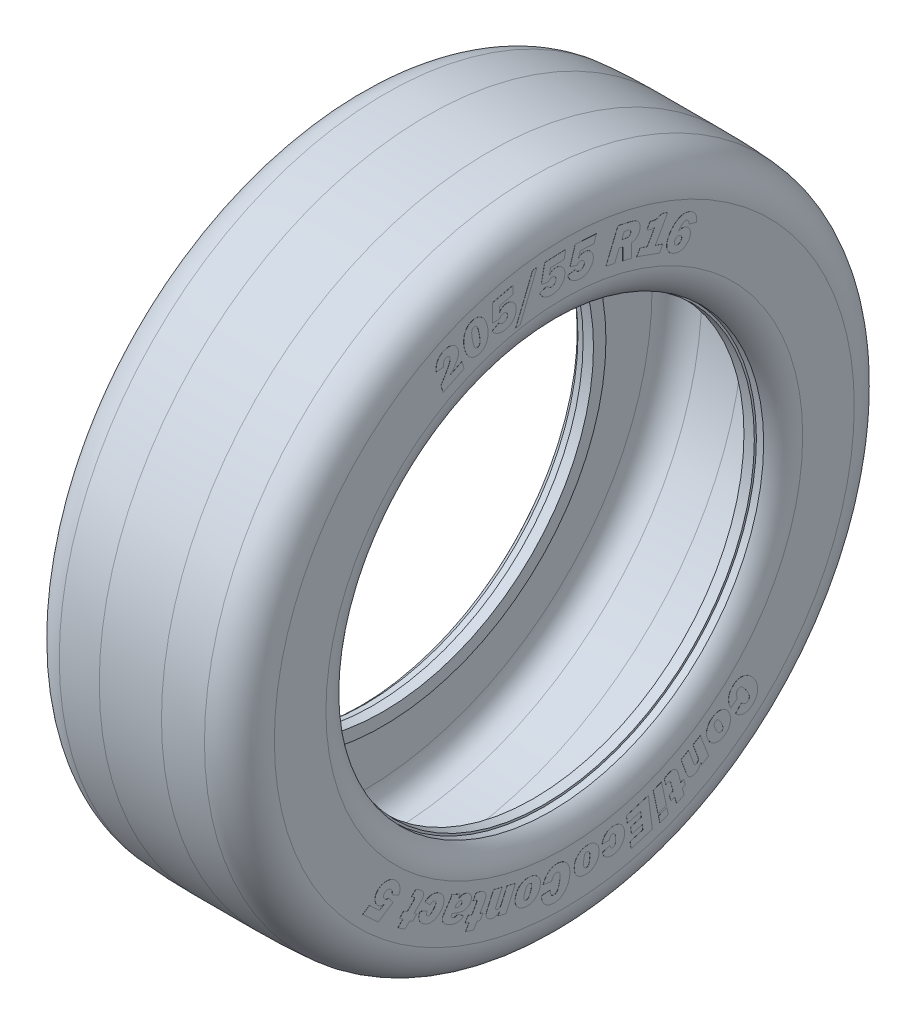
SolidWorks part; units mm, degrees
ref_plane "Płaszczyzna przednia" through (0, 0, 0) normal (0, 0, 1) x (1, 0, 0)
ref_plane "Płaszczyzna górna" through (0, 0, 0) normal (0, 1, 0) x (1, 0, 0)
ref_plane "Płaszczyzna prawa" through (0, 0, 0) normal (1, 0, 0) x (0, 0, -1)
sketch "Szkic1" plane through (0, 0, 0) normal (0, 0, 1) x (1, 0, 0)
  line L0 (-110.3721, 0) -> (107.9596, 0) construction
  line L1 (0, -110.9753) -> (0, 229.1683) construction
  line L2 (-72.55, 203.2) -> (-82.55, 203.2)
  line L3 (-82.55, 203.2) -> (-82.55, 205.2)
  line L4 (-82.55, 205.2) -> (-89.55, 205.2)
  line L5 (0, 315.95) -> (-30, 315.95)
  line L6 (-102.5, 229.884) -> (-102.5, 279.609)
  line L7 (72.55, 213.2) -> (72.55, 213.2)
  line L12 (72.55, 213.2) -> (72.55, 215.2)
  line L13 (72.55, 215.2) -> (86.0787, 215.2)
  line L16 (82.55, 205.2) -> (89.55, 205.2)
  line L17 (82.55, 203.2) -> (82.55, 205.2)
  line L18 (72.55, 203.2) -> (82.55, 203.2)
  line L23 (102.5, 229.884) -> (102.5, 279.609)
  line L25 (0, 315.95) -> (30, 315.95)
  line L26 (92.5, 229.884) -> (92.5, 279.609)
  line L27 (0, 305.95) -> (30, 305.95)
  line L28 (0, 305.95) -> (-30, 305.95)
  line L29 (-92.5, 229.884) -> (-92.5, 279.609)
  line L30 (-72.55, 215.2) -> (-86.0787, 215.2)
  line L31 (-72.55, 213.2) -> (-72.55, 215.2)
  line L32 (-72.55, 213.2) -> (-72.55, 213.2)
  line L33 (-72.55, 213.2) -> (-72.55, 203.2)
  line L34 (72.55, 213.2) -> (72.55, 203.2)
  arc A1 (-89.55, 205.2) -> (-102.5, 229.884) centre (-72.5, 229.884) cw
  arc A3 (-70, 314.5196) -> (-102.5, 279.609) centre (-67.5, 279.609) ccw
  arc A4 (-70, 314.5196) -> (-30, 315.95) centre (-30, -244.05) cw
  arc A9 (89.55, 205.2) -> (102.5, 229.884) centre (72.5, 229.884) ccw
  arc A11 (70, 314.5196) -> (102.5, 279.609) centre (67.5, 279.609) cw
  arc A13 (70, 314.5196) -> (30, 315.95) centre (30, -244.05) ccw
  arc A14 (86.0787, 215.2) -> (92.5, 229.884) centre (72.5, 229.884) ccw
  arc A15 (69.2857, 304.5451) -> (92.5, 279.609) centre (67.5, 279.609) cw
  arc A16 (69.2857, 304.5451) -> (30, 305.95) centre (30, -244.05) ccw
  arc A17 (-69.2857, 304.5451) -> (-30, 305.95) centre (-30, -244.05) cw
  arc A18 (-69.2857, 304.5451) -> (-92.5, 279.609) centre (-67.5, 279.609) ccw
  arc A19 (-86.0787, 215.2) -> (-92.5, 229.884) centre (-72.5, 229.884) cw
  dimension "D5" = 205
  dimension "D9" = 40
  dimension "D10" = 35
  dimension "D11" = 30
  dimension "D1" = 406.4
  dimension "D2" = 10
  dimension "D3" = 2
  dimension "D4" = 7
  dimension "D6" = 631.9
  dimension "D7" = 30
  dimension "D8" = 165.1
  dimension "D12" = 10
revolve "Obrót1" add sketch "Szkic1" angle 360 about L0 region at (-77.55, 205.5396, 0)
sketch "Szkic2" plane through (102.5, 0, 0) normal (1, 0, 0) x (0, 0, -1)
  line L0 (-229.3059, 160) -> (229.3059, 160) construction
  line L1 (112.75, 0) -> (-112.75, 0) construction
  line L2 (-229.3059, -160) -> (229.3059, -160) construction
  arc A0 (-178.8854, -160) -> (178.8854, -160) centre (0, 0) ccw construction
  circle A1 centre (0, 0) radius 279.609 construction
  arc A2 (178.8854, 160) -> (-178.8854, 160) centre (0, 0) ccw construction
  text T0 "205/55 R16" font "Franklin Gothic Heavy" height 30
  text T1 "ContiEcoContact 5" font "Franklin Gothic Heavy" height 30
  dimension "D1" = 480
  dimension "D2" = 160
extrude "Dodanie-wyciągnięcie1" add sketch "Szkic2" along normal blind 0.1
sketch "Szkic3" plane through (-102.5, 0, 0) normal (-1, 0, 0) x (0, 0, 1)
  line L0 (-229.3059, 160) -> (229.3059, 160) construction
  line L1 (112.805, 0) -> (-112.805, 0) construction
  line L2 (-229.3059, -160) -> (229.3059, -160) construction
  arc A0 (-178.8854, -160) -> (178.8854, -160) centre (0, 0) ccw construction
  circle A1 centre (0, 0) radius 279.609 construction
  arc A2 (178.8854, 160) -> (-178.8854, 160) centre (0, 0) ccw construction
  text T0 "205/55 R16" font "Franklin Gothic Heavy" height 30
  text T1 "ContiEcoContact 5" font "Franklin Gothic Heavy" height 30
  dimension "D1" = 480
  dimension "D2" = 160
extrude "Dodanie-wyciągnięcie2" add sketch "Szkic3" along normal blind 0.1
